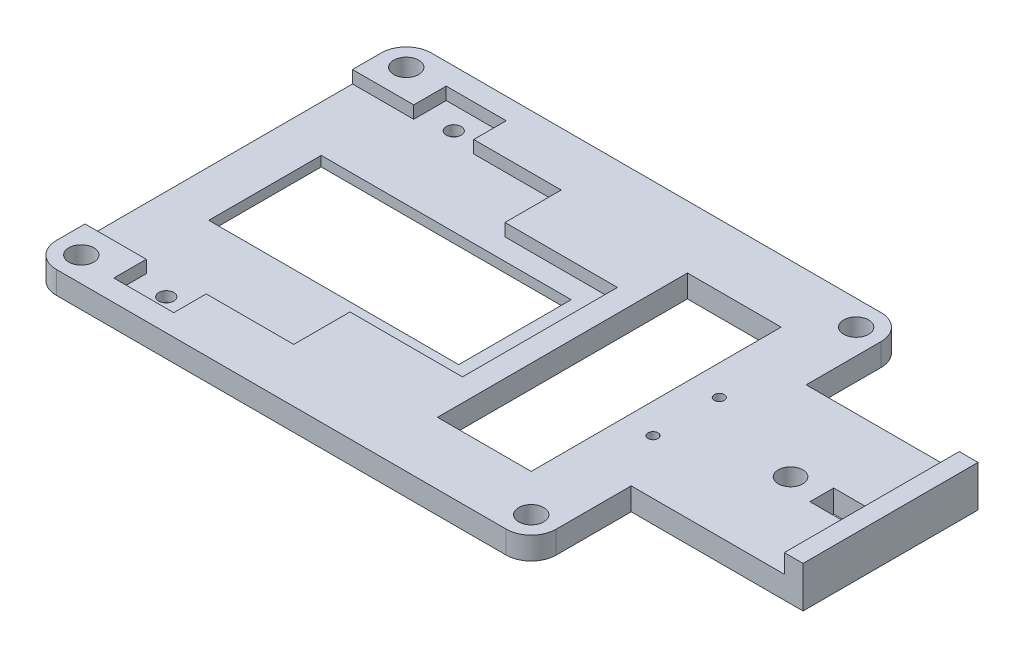
SolidWorks part; units mm, degrees
ref_plane "Front Plane" through (0, 0, 0) normal (0, 0, 1) x (1, 0, 0)
ref_plane "Top Plane" through (0, 0, 0) normal (0, 1, 0) x (1, 0, 0)
ref_plane "Right Plane" through (0, 0, 0) normal (1, 0, 0) x (0, 0, -1)
sketch "Sketch2" plane through (0, 0, 0) normal (0, 1, 0) x (1, 0, 0)
  line L1 (68.2625, -38.1) -> (-68.2625, -38.1)
  line L2 (68.2625, -38.1) -> (68.2625, 38.1)
  line L3 (68.2625, 38.1) -> (-68.2625, 38.1)
  line L4 (-68.2625, -38.1) -> (-68.2625, 38.1)
  line L5 (68.2625, -38.1) -> (-68.2625, 38.1) construction
  line L6 (68.2625, 38.1) -> (-68.2625, -38.1) construction
  point P0 (0, 0)
  dimension "D1" = 76.2
  dimension "D2" = 136.525
extrude "Chassis Base" add sketch "Sketch2" along normal blind 4.572
extrude "Boss-Extrude2" add sketch "Sketch2<2>" along normal blind 4.572
sketch "Sketch2<2>" plane through (0, 0, 0) normal (0, 1, 0) x (1, 0, 0) same geometry as "Sketch2"
sketch "Sketch4" plane through (0, 0, 0) normal (0, -1, 0) x (1, 0, 0)
  line L0 (-68.2625, 0) -> (68.2625, 0) construction
  line L1 (68.2625, -38.1) -> (33.3375, -38.1)
  line L2 (68.2625, -38.1) -> (68.2625, -17.78)
  line L3 (68.2625, -17.78) -> (33.3375, -17.78)
  line L4 (33.3375, -38.1) -> (33.3375, -17.78)
  line L5 (-68.2625, 38.1) -> (-68.2625, -38.1) construction
  line L6 (68.2625, 38.1) -> (68.2625, -38.1) construction
  line L7 (68.2625, 17.78) -> (33.3375, 17.78)
  line L8 (33.3375, 38.1) -> (33.3375, 17.78)
  line L9 (68.2625, 38.1) -> (33.3375, 38.1)
  line L10 (68.2625, 38.1) -> (68.2625, 17.78)
  dimension "D1" = 34.925
  dimension "D2" = 20.32
extrude "Corner Cutouts" cut sketch "Sketch4" against normal through all
sketch "Lines" plane through (0, 4.572, 0) normal (0, 1, 0) x (1, 0, 0)
  line L0 (-68.2625, 0) -> (68.2625, 0) construction
  line L1 (-68.2625, -38.1) -> (-68.2625, 38.1) construction
  line L2 (68.2625, -38.1) -> (68.2625, 38.1) construction
  line L3 (-68.2625, -27.178) -> (-55.8165, -27.178)
  line L4 (-55.8165, -27.178) -> (-55.8165, -33.782)
  line L7 (-55.8165, -33.782) -> (-43.6245, -33.782)
  line L8 (-43.6245, -33.782) -> (-43.6245, -27.178)
  line L9 (-43.6245, -27.178) -> (-25.8445, -27.178)
  line L10 (-25.8445, -27.178) -> (-25.8445, -15.748)
  line L12 (-68.2625, -27.178) -> (-68.2625, 27.178)
  line L13 (-25.8445, -15.748) -> (-2.9845, -15.748)
  line L14 (-2.9845, -15.748) -> (-2.9845, 15.748)
  line L15 (-25.8445, 15.748) -> (-2.9845, 15.748)
  line L16 (-25.8445, 27.178) -> (-25.8445, 15.748)
  line L17 (-43.6245, 27.178) -> (-25.8445, 27.178)
  line L18 (-43.6245, 33.782) -> (-43.6245, 27.178)
  line L19 (-55.8165, 33.782) -> (-43.6245, 33.782)
  line L20 (-55.8165, 27.178) -> (-55.8165, 33.782)
  line L21 (-68.2625, 27.178) -> (-55.8165, 27.178)
  point P16 (-2.9845, 0)
  dimension "D1" = 12.192
  dimension "D2" = 6.604
  dimension "D3" = 17.78
  dimension "D4" = 27.178
  dimension "D5" = 6.604
  dimension "D6" = 11.43
  dimension "D7" = 22.86
  dimension "D8" = 12.446
extrude "Cut-Extrude2" cut sketch "Lines" against normal blind 2.54
sketch "Circle" plane through (0, 2.032, 0) normal (0, 1, 0) x (1, 0, 0)
  line L2 (-55.8165, -27.178) -> (-55.8165, -33.782) construction
  line L5 (-55.8165, -33.782) -> (-43.6245, -33.782) construction
  line L6 (-68.2625, 0) -> (68.2625, 0) construction
  line L9 (-68.2625, -38.1) -> (-68.2625, 38.1) construction
  line L10 (68.2625, -17.78) -> (68.2625, 17.78) construction
  circle A0 centre (-49.7205, -29.21) radius 1.524
  circle A1 centre (-49.7205, 29.21) radius 1.524
  point P8 (0, 0)
  point P9 (0, 0)
  point P10 (0, 0)
  point P12 (0, 0)
  point P16 (0, 0)
  dimension "D1" = 6.096
  dimension "D3" = 3.048
  dimension "D2" = 4.572
extrude "Circle Through All" cut sketch "Circle" against normal through all
fillet "Fillet4" radius 5.08 4 edges at (33.3375, 2.286, -38.1) (-68.2625, 2.286, -38.1) (-68.2625, 2.286, 38.1) (33.3375, 2.286, 38.1)
sketch "Sketch10" plane through (0, 2.032, 0) normal (0, 1, 0) x (1, 0, 0)
  line L0 (-68.2625, 0) -> (68.2625, 0) construction
  line L1 (-68.2625, -38.1) -> (-68.2625, 38.1) construction
  line L2 (68.2625, -17.78) -> (68.2625, 17.78) construction
  line L4 (-8.0645, -11.43) -> (-58.8645, -11.43)
  line L5 (-8.0645, -11.43) -> (-8.0645, 11.43)
  line L6 (-8.0645, 11.43) -> (-58.8645, 11.43)
  line L7 (-58.8645, -11.43) -> (-58.8645, 11.43)
  line L8 (-8.0645, -11.43) -> (-58.8645, 11.43) construction
  line L9 (-8.0645, 11.43) -> (-58.8645, -11.43) construction
  point P6 (-33.4645, 0)
  dimension "D1" = 9.398
  dimension "D2" = 22.86
  dimension "D3" = 50.8
extrude "resistance sensor" cut sketch "Sketch10" against normal through all
sketch "Sketch11" plane through (0, 4.572, 0) normal (0, 1, 0) x (1, 0, 0)
  line L0 (68.2625, 38.1) -> (-68.2625, 38.1) construction
  line L1 (-68.2625, -38.1) -> (-68.2625, 38.1) construction
  line L2 (-68.2625, 0) -> (68.2625, 0) construction
  line L3 (68.2625, -38.1) -> (68.2625, 38.1) construction
  line L4 (-17.4625, 38.1) -> (-17.4625, -38.1) construction
  line L5 (-63.1825, -38.1) -> (28.2575, -38.1) construction
  circle A0 centre (-63.1825, 33.02) radius 2.54
  circle A1 centre (28.2575, 33.02) radius 2.54
  circle A2 centre (-63.1825, -33.02) radius 2.54
  circle A3 centre (28.2575, -33.02) radius 2.54
  dimension "D1" = 5.08
  dimension "D2" = 5.08
  dimension "D4" = 5.08
  dimension "D3" = 50.8
extrude "corner holes" cut sketch "Sketch11" against normal through all
sketch "Sketch12" plane through (0, 2.032, 0) normal (0, 1, 0) x (1, 0, 0)
  line L0 (-68.2625, 0) -> (68.2625, 0) construction
  line L1 (-68.2625, -38.1) -> (-68.2625, 38.1) construction
  line L2 (68.2625, -17.78) -> (68.2625, 17.78) construction
  line L3 (68.2625, -17.78) -> (57.2135, -17.78) construction
  line L10 (1.5875, -25.4) -> (20.6375, -25.4)
  line L11 (1.5875, -25.4) -> (1.5875, 25.4)
  line L12 (1.5875, 25.4) -> (20.6375, 25.4)
  line L13 (20.6375, -25.4) -> (20.6375, 25.4)
  line L14 (1.5875, -25.4) -> (20.6375, 25.4) construction
  line L15 (1.5875, 25.4) -> (20.6375, -25.4) construction
  line L16 (-2.9845, -15.748) -> (-2.9845, 15.748) construction
  circle A1 centre (26.7335, -6.731) radius 1.016
  circle A2 centre (26.7335, 6.731) radius 1.016
  point P8 (57.4675, 0)
  point P14 (11.1125, 0)
  point P23 (0, 0)
  point P24 (0, 0)
  point P25 (0, 0)
  point P26 (0, 0)
  dimension "D6" = 2.032
  dimension "D2" = 19.05
  dimension "D7" = 11.049
  dimension "D9" = 6.096
  dimension "D10" = 50.8
  dimension "D11" = 4.572
extrude "Cut-Extrude7" cut sketch "Sketch12" against normal through all both and the other way through all
sketch "Sketch16" plane through (0, 4.572, 0) normal (0, 1, 0) x (1, 0, 0)
  line L0 (68.6243, 0) -> (-68.2625, 0) construction
  line L2 (-68.2625, -38.1) -> (-68.2625, 38.1) construction
  line L3 (68.2625, -38.1) -> (68.2625, 38.1) construction
  line L4 (60.6425, -2.413) -> (54.2925, -2.413)
  line L5 (60.6425, -2.413) -> (60.6425, 2.413)
  line L6 (60.6425, 2.413) -> (54.2925, 2.413)
  line L7 (54.2925, -2.413) -> (54.2925, 2.413)
  line L8 (60.6425, -2.413) -> (54.2925, 2.413) construction
  line L9 (60.6425, 2.413) -> (54.2925, -2.413) construction
  point P5 (57.4675, 0)
  point P10 (0, 0)
  point P11 (0, 0)
  dimension "D1" = 4.826
  dimension "D2" = 6.35
  dimension "D3" = 7.62
extrude "Cut-Extrude11" cut sketch "Sketch16" against normal through all
sketch "Sketch17" plane through (0, 4.572, 0) normal (0, 1, 0) x (1, 0, 0)
  line L0 (-68.2625, 0) -> (68.2625, 0) construction
  line L1 (-68.2625, -38.1) -> (-68.2625, 38.1) construction
  line L2 (68.2625, -38.1) -> (68.2625, 38.1) construction
  line L3 (54.2925, 2.413) -> (54.2925, -2.413) construction
  circle A0 centre (47.9425, 0) radius 2.4892
  point P8 (0, 0)
  dimension "D1" = 6.35
  dimension "D2" = 4.9784
extrude "Cut-Extrude12" cut sketch "Sketch17" against normal through all contours A0
sketch "Sketch18" plane through (0, 0, 0) normal (0, -1, 0) x (1, 0, 0)
  text T0 "Tom  Fu" font "Charlemagne Std" height 5.08
extrude "Cut-Extrude13" cut sketch "Sketch18" against normal blind 1.27
sketch "Sketch19" plane through (0, 4.572, 0) normal (0, 1, 0) x (1, 0, 0)
  line L0 (33.3375, -17.78) -> (68.2625, -17.78) construction
  line L1 (68.2625, 17.78) -> (64.4525, 17.78)
  line L2 (68.2625, 17.78) -> (68.2625, -17.78)
  line L3 (68.2625, -17.78) -> (64.4525, -17.78)
  line L4 (64.4525, 17.78) -> (64.4525, -17.78)
  dimension "D1" = 3.81
extrude "Boss-Extrude4" add sketch "Sketch19" along normal blind 3.81
